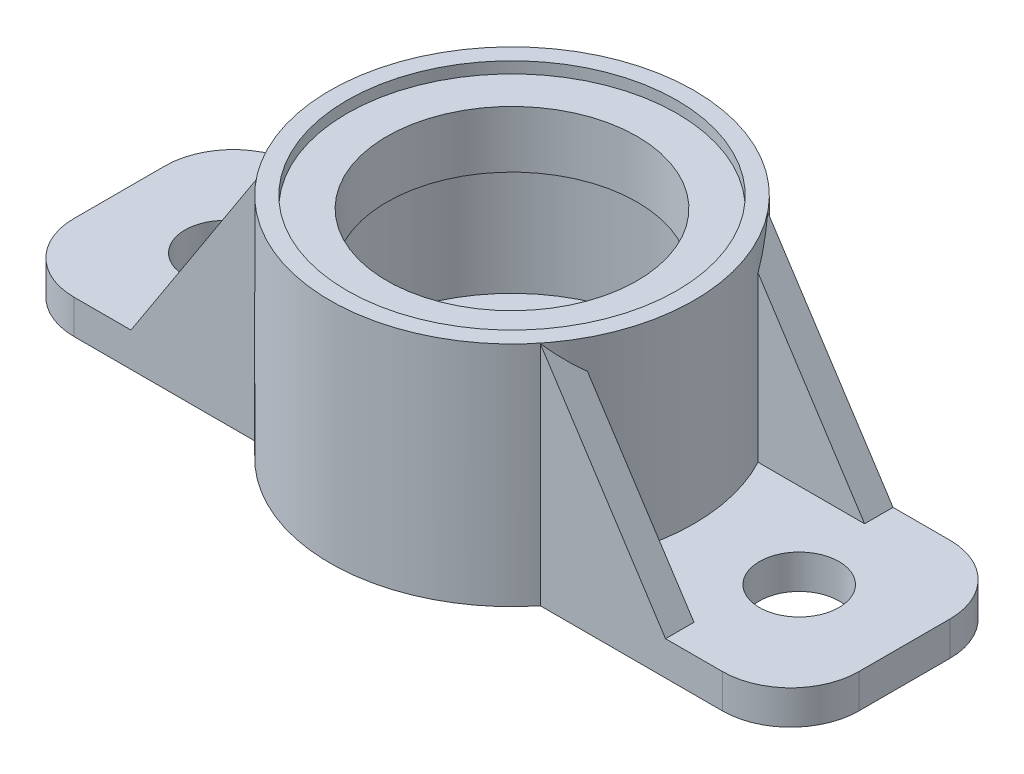
SolidWorks part; units mm, degrees
ref_plane "Front Plane" through (0, 0, 0) normal (0, 0, 1) x (1, 0, 0)
ref_plane "Top Plane" through (0, 0, 0) normal (0, 1, 0) x (1, 0, 0)
ref_plane "Right Plane" through (0, 0, 0) normal (1, 0, 0) x (0, 0, -1)
sketch "Sketch2" plane through (0, 0, 0) normal (0, 1, 0) x (1, 0, 0)
  line L0 (0, 50.8) -> (0, -50.8) construction
  line L1 (-175.26, -50.8) -> (175.26, -50.8)
  line L2 (-175.26, -50.8) -> (-175.26, 50.8)
  line L3 (-175.26, 50.8) -> (175.26, 50.8)
  line L4 (175.26, -50.8) -> (175.26, 50.8)
  line L5 (-175.26, -50.8) -> (175.26, 50.8) construction
  line L6 (-175.26, 50.8) -> (175.26, -50.8) construction
  circle A1 centre (0, 0) radius 43.18
  circle A2 centre (128.27, 0) radius 17.78
  circle A3 centre (-128.27, 0) radius 17.78
  circle A4 centre (0, 0) radius 20.32
  dimension "D1" = 40.64
  dimension "D2" = 86.36
  dimension "D5" = 35.56
  dimension "D6" = 50.8
  dimension "D3" = 101.6
  dimension "D4" = 350.52
  dimension "D7" = 46.99
extrude "Boss-Extrude1" add sketch "Sketch2" along normal blind 15.24 contours L1 L4 L3 L2 A1 A2 A3 region at (-171.6105, 0, 0)
extrude "Boss-Extrude2" add sketch "Sketch2<3>" along normal blind 10.16 contours A1 A4 region at (-41.9587, 0, 0)
sketch "Sketch2<3>" plane through (0, 0, 0) normal (0, 1, 0) x (1, 0, 0) same geometry as "Sketch2"
sketch "Sketch3" plane through (0, 0, 0) normal (0, 0, 1) x (1, 0, 0)
  line L2 (81.28, 0) -> (81.28, 101.6)
  line L3 (81.28, 101.6) -> (73.66, 101.6)
  line L4 (73.66, 101.6) -> (73.66, 96.52)
  line L5 (73.66, 96.52) -> (55.88, 96.52)
  line L6 (55.88, 96.52) -> (55.88, 71.12)
  line L7 (55.88, 71.12) -> (68.58, 71.12)
  line L8 (68.58, 71.12) -> (68.58, 15.24)
  line L9 (0, 0) -> (0, 146.0119) construction
  line L10 (-175.26, 0) -> (175.26, 0) construction
  line L12 (-175.26, 15.24) -> (175.26, 15.24) construction
  line L13 (0, 15.24) -> (0, 0)
  line L15 (68.58, 15.24) -> (43.18, 15.24)
  line L16 (43.18, 15.24) -> (43.18, 0)
  line L17 (43.18, 0) -> (81.28, 0)
  point P11 (81.28, 0)
  dimension "D1" = 81.28
  dimension "D2" = 101.6
  dimension "D3" = 12.7
  dimension "D4" = 55.88
  dimension "D5" = 55.88
  dimension "D6" = 73.66
  dimension "D7" = 96.52
  dimension "D8" = 43.18
revolve "Revolve1" add sketch "Sketch3" angle 360 about L9 region at (69.1693, 47.0979, 0)
sketch "Sketch4" plane through (0, 0, 0) normal (0, 0, 1) x (1, 0, 0)
  line L0 (119.38, 15.24) -> (63.2972, 101.6)
  line L1 (63.4492, 15.24) -> (175.26, 15.24) construction
  line L2 (81.28, 101.6) -> (-81.28, 101.6) construction
  line L3 (63.2972, 101.6) -> (63.2972, 15.24)
  line L4 (63.2972, 15.24) -> (119.38, 15.24)
  line L5 (0, 0) -> (0, 132.696) construction
  line L7 (-63.2972, 15.24) -> (-119.38, 15.24)
  line L8 (-63.2972, 101.6) -> (-63.2972, 15.24)
  line L9 (-119.38, 15.24) -> (-63.2972, 101.6)
  point P10 (0, 0)
  dimension "D1" = 57
  dimension "D2" = 55.88
extrude "Boss-Extrude3" add sketch "Sketch4" along normal blind 12.7 from surface starting at face at (119.3546, 7.62, -50.8)
extrude "Boss-Extrude4" add sketch "Sketch4<2>" against normal blind 12.7 from surface starting at face at (119.3546, 7.62, 50.8)
sketch "Sketch4<2>" plane through (0, 0, 0) normal (0, 0, 1) x (1, 0, 0) same geometry as "Sketch4"
fillet "Fillet1" radius 30.48 4 edges at (-175.26, 7.62, -50.8) (-175.26, 7.62, 50.8) (175.26, 7.62, -50.8) (175.26, 7.62, 50.8)
